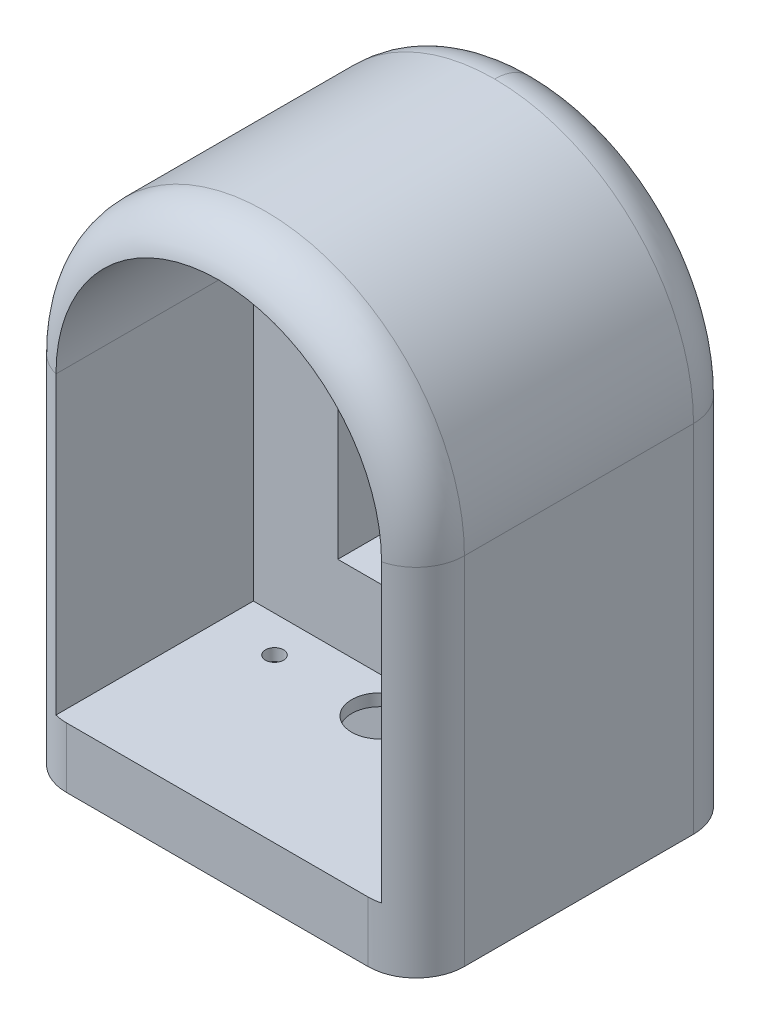
SolidWorks part; units mm, degrees
ref_plane "Front Plane" through (0, 0, 0) normal (0, 0, 1) x (1, 0, 0)
ref_plane "Top Plane" through (0, 0, 0) normal (0, 1, 0) x (1, 0, 0)
ref_plane "Right Plane" through (0, 0, 0) normal (1, 0, 0) x (0, 0, -1)
sketch "Sketch1" plane through (0, 0, 0) normal (0, 1, 0) x (1, 0, 0)
  line L1 (-16.5, -13.5) -> (16.5, -13.5)
  line L2 (-16.5, -13.5) -> (-16.5, 13.5)
  line L3 (-16.5, 13.5) -> (16.5, 13.5)
  line L4 (16.5, -13.5) -> (16.5, 13.5)
  line L5 (-16.5, -13.5) -> (16.5, 13.5) construction
  line L6 (-16.5, 13.5) -> (16.5, -13.5) construction
  point P0 (0, 0)
  dimension "D1" = 33
  dimension "D2" = 27
extrude "Boss-Extrude1" add sketch "Sketch1" along normal blind 46
sketch "Sketch3" plane through (16.5, 0, 0) normal (1, 0, 0) x (0, 0, -1)
  line L2 (-13.5, 0) -> (13.5, 0) construction
  line L3 (13.5, 46) -> (11, 46)
  line L4 (13.5, 46) -> (13.5, 21)
  line L5 (13.5, 21) -> (11, 21)
  line L6 (11, 46) -> (11, 21)
  line L7 (-13.5, 46) -> (3, 46)
  line L8 (-13.5, 46) -> (-13.5, 5)
  line L9 (-13.5, 5) -> (3, 5)
  line L10 (3, 46) -> (3, 5)
  line M11 (13.5, 46) -> (-13.5, 46)
  line M12 (-13.5, 46) -> (-13.5, 0)
  dimension "D1" = 5
  dimension "D2" = 8
  dimension "D3" = 2.5
  dimension "D4" = 25
extrude "Cut-Extrude2" cut sketch "Sketch3" against normal through all contours L10 L9 M11 M12 region at (16.5, 25.5, 5.25)
sketch "Sketch4" plane through (0, 0, 0) normal (0, -1, 0) x (1, 0, 0)
  line L0 (-16.5, -13.5) -> (-16.5, 13.5) construction
  line L1 (0, 0) -> (14, 0)
  line L2 (0.1339, 2.4964) -> (14.0938, 1.7475)
  line L3 (0.1339, -2.4964) -> (14.0938, -1.7475)
  line L4 (0, 0) -> (0, 2.5)
  line L5 (-0.1339, -2.4964) -> (-14.0938, -1.7475)
  line L6 (-0.1339, 2.4964) -> (-14.0938, 1.7475)
  arc A0 (0.1339, 2.4964) -> (-0.1339, 2.4964) centre (0, 0) ccw
  arc A1 (14.0938, -1.7475) -> (14.0938, 1.7475) centre (14, 0) ccw
  arc A2 (-14.0938, -1.7475) -> (-14.0938, 1.7475) centre (-14, 0) cw
  arc A3 (-0.1339, -2.4964) -> (0.1339, -2.4964) centre (0, 0) ccw
  dimension "D2" = 5
  dimension "D1" = 16.5
fillet "Fillet3" radius 16.5 2 edges at (-16.5, 46, -8.25) (16.5, 46, -8.25)
sketch "Sketch9" plane through (0, 0, -3) normal (0, 0, 1) x (1, 0, 0)
  line L0 (-16.5, 5) -> (16.5, 5) construction
  line L1 (-6.5, 11.5) -> (6.5, 11.5)
  line L2 (-6.5, 11.5) -> (-6.5, 34.5)
  line L3 (-6.5, 34.5) -> (6.5, 34.5)
  line L4 (6.5, 11.5) -> (6.5, 34.5)
  line L5 (-6.5, 11.5) -> (6.5, 34.5) construction
  line L6 (-6.5, 34.5) -> (6.5, 11.5) construction
  point P0 (0, 23)
  dimension "D1" = 13
  dimension "D2" = 23
  dimension "D3" = 6.5
extrude "Cut-Extrude4" cut sketch "Sketch9" against normal blind 9
sketch "Sketch10" plane through (0, 0, -12) normal (0, 0, 1) x (1, 0, 0)
  line L1 (6.5, 34.5) -> (-6.5, 34.5) construction
  circle A0 centre (0, 28) radius 6.5
  dimension "D1" = 13
  dimension "D2" = 6.5
extrude "Cut-Extrude5" cut sketch "Sketch10" against normal through all
sketch "Sketch11" plane through (0, 0, -3) normal (0, 0, 1) x (1, 0, 0)
  line L1 (6.5, 34.5) -> (0, 34.5) construction
  circle A0 centre (0, 36.8) radius 1
  circle A1 centre (0, 9.2) radius 1
  dimension "D1" = 27.6
  dimension "D2" = 2
  dimension "D3" = 2
  dimension "D4" = 2.3
extrude "Cut-Extrude6" cut sketch "Sketch11" against normal blind 8
sketch "Sketch15" plane through (0, 0, -3) normal (0, 0, 1) x (1, 0, 0)
  line L3 (13.5, 5) -> (13.5, 29.5)
  line L4 (13.5, 5) -> (13.5, 29.5)
  line L5 (16.5, 5) -> (16.5, 29.5)
  line L6 (-13.5, 29.5) -> (-13.5, 5)
  line L7 (-13.5, 29.5) -> (-13.5, 5)
  line L8 (-16.5, 29.5) -> (-16.5, 5)
  line L9 (-16.5, 5) -> (-13.5, 5)
  line L10 (13.5, 5) -> (16.5, 5)
  arc A11 (16.5, 29.5) -> (0, 46) centre (0, 29.5) ccw
  arc A12 (0, 46) -> (-16.5, 29.5) centre (0, 29.5) ccw
  arc A13 (13.5, 29.5) -> (0, 43) centre (0, 29.5) ccw
  arc A14 (0, 43) -> (-13.5, 29.5) centre (0, 29.5) ccw
  arc A15 (13.5, 29.5) -> (0, 43) centre (0, 29.5) ccw
  arc A16 (0, 43) -> (-13.5, 29.5) centre (0, 29.5) ccw
  dimension "D1" = 3
  dimension "D2" = 3
  dimension "D3" = 3
extrude "Boss-Extrude7" add sketch "Sketch15" along normal blind 16.5
fillet "Fillet5" radius 4 6 edges at (16.5, 14.75, 13.5) (-16.5, 14.75, 13.5) (-16.5, 14.75, -13.5) (16.5, 14.75, -13.5) (11.6673, 41.1673, -13.5) (-11.6673, 41.1673, -13.5)
extrude "Cut-Extrude7" cut sketch "Sketch4" against normal blind 4 contours L5 A3 L3 A1 L2 A0 L6 A2 region at (7.0968, 0, 1.8035)
sketch "Sketch17" plane through (0, 4, 0) normal (0, -1, 0) x (1, 0, 0)
  circle A0 centre (0, 0) radius 1.3
extrude "Cut-Extrude8" cut sketch "Sketch17" against normal blind 1.75
sketch "Sketch18" plane through (0, 5, 0) normal (0, 1, 0) x (1, 0, 0)
  circle A0 centre (0, 0) radius 2.35
extrude "Cut-Extrude9" cut sketch "Sketch18" against normal blind 1
sketch "Sketch19" plane through (0, 4, 0) normal (0, -1, 0) x (1, 0, 0)
  line L0 (0, 0) -> (-8, 0)
  line L1 (0, 0) -> (8, 0)
  circle A2 centre (-8.75, 0) radius 0.75
  circle A3 centre (8.75, 0) radius 0.75
extrude "Cut-Extrude10" cut sketch "Sketch19" against normal blind 1.75 contours A2 | A3 region at (-8.75, 4, 0)
